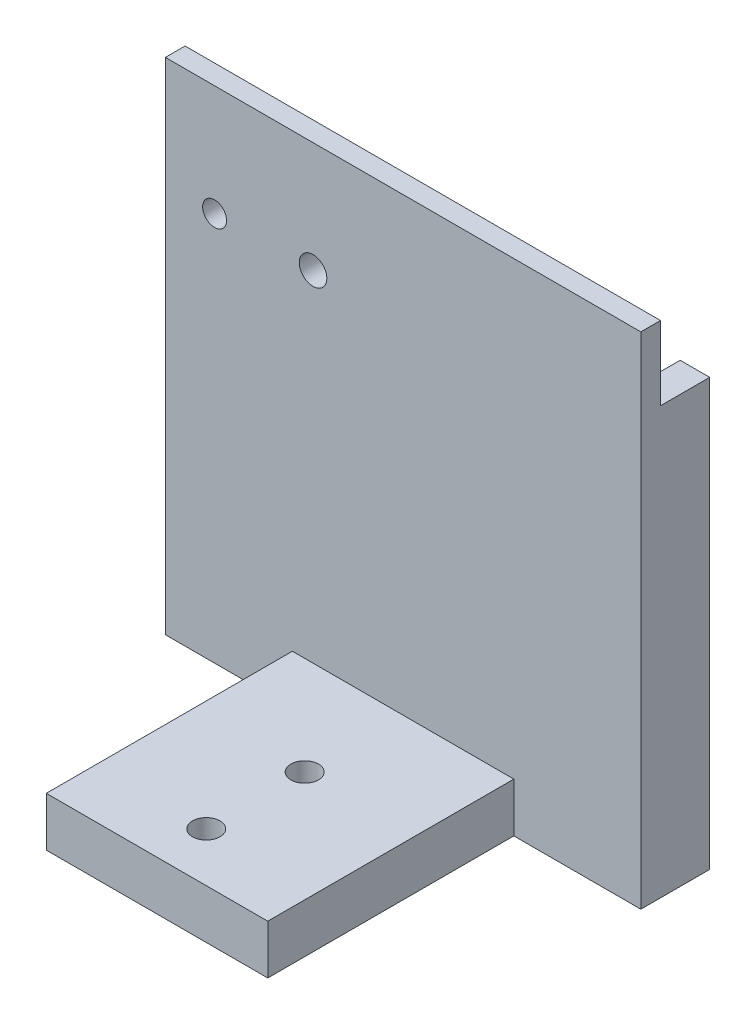
SolidWorks part; units mm, degrees
ref_plane "Front Plane" through (0, 0, 0) normal (0, 0, 1) x (1, 0, 0)
ref_plane "Top Plane" through (0, 0, 0) normal (0, 1, 0) x (1, 0, 0)
ref_plane "Right Plane" through (0, 0, 0) normal (1, 0, 0) x (0, 0, -1)
sketch "Sketch1" plane through (0, 0, 0) normal (0, 0, 1) x (1, 0, 0)
  line L0 (-17.15, 21.15) -> (17.15, 21.15) construction
  line L1 (21.15, -21.15) -> (-21.15, -21.15)
  line L2 (21.15, -21.15) -> (21.15, 21.15)
  line L3 (21.15, 21.15) -> (-21.15, 21.15)
  line L4 (-21.15, -21.15) -> (-21.15, 21.15)
  line L5 (-21.15, -17.15) -> (-21.15, 17.15) construction
  line L6 (21.15, 17.15) -> (21.15, -17.15) construction
  line L7 (17.15, -21.15) -> (-17.15, -21.15) construction
  line L9 (24.15, -22.15) -> (-24.15, -22.15)
  line L10 (24.15, -22.15) -> (24.15, 21.15)
  line L11 (24.15, 21.15) -> (-24.15, 21.15)
  line L12 (-24.15, -22.15) -> (-24.15, 21.15)
  point P16 (-21.15, 0)
  dimension "D1" = 0
  dimension "D2" = 0
  dimension "D3" = 0
  dimension "D4" = 0
  dimension "D5" = 3
  dimension "D6" = 3
  dimension "D7" = 1
  dimension "D8" = 0
extrude "Boss-Extrude1" add sketch "Sketch1" along normal blind 2 contours L4 L1 L2 L3 | L12 L9 L10 L11 L2 L1 L4 region at (21.7987, 0, 0) region at (0, 0, 0)
extrude "Boss-Extrude2" add sketch "Sketch1<3>" against normal blind 5 contours L12 L9 L10 L11 L2 L1 L4 region at (21.7987, 0, 0)
sketch "Sketch1<3>" plane through (0, 0, 0) normal (0, 0, 1) x (1, 0, 0) same geometry as "Sketch1"
sketch "Sketch2" plane through (0, 0, 2) normal (0, 0, 1) x (1, 0, 0)
  line L0 (24.15, -22.15) -> (-24.15, -22.15) construction
  line L1 (11.25, -22.15) -> (-11.25, -22.15)
  line L2 (11.25, -22.15) -> (11.25, -17.15)
  line L3 (11.25, -17.15) -> (-11.25, -17.15)
  line L4 (-11.25, -22.15) -> (-11.25, -17.15)
  line L5 (24.15, -22.15) -> (24.15, 21.15) construction
  dimension "D1" = 22.5
  dimension "D2" = 12.9
  dimension "D3" = 5
extrude "Boss-Extrude3" add sketch "Sketch2" along normal blind 25
sketch "Sketch3" plane through (0, 0, 2) normal (0, 0, 1) x (1, 0, 0)
  line L0 (-110.3641, 28.649) -> (-55.8641, 28.649) construction
  line L1 (-24.15, 6.149) -> (24.15, 6.149)
  line L2 (-24.15, 6.149) -> (-24.15, 28.649)
  line L3 (-24.15, 28.649) -> (24.15, 28.649)
  line L4 (24.15, 6.149) -> (24.15, 28.649)
  line L5 (24.15, -22.15) -> (24.15, 21.15) construction
  line L6 (-24.15, -22.15) -> (-24.15, 21.15) construction
  circle A0 centre (-19.15, 17.399) radius 1.2149
  circle A1 centre (-9.15, 17.399) radius 1.4
  dimension "D5" = 10
  dimension "D6" = 5
  dimension "D7" = 2.8
  dimension "D8" = 11.25
  dimension "D9" = 11.25
  dimension "D1" = 0
  dimension "D2" = 22.5
  dimension "D3" = 0
  dimension "D4" = 0
extrude "Boss-Extrude4" add sketch "Sketch3" against normal blind 2
sketch "Sketch4" plane through (0, -17.15, 0) normal (0, 1, 0) x (1, 0, 0)
  line L0 (11.25, -27) -> (-11.25, -27) construction
  line L1 (-11.25, -27) -> (-11.25, -2) construction
  circle A0 centre (0, -12) radius 1.4
  circle A1 centre (0, -22) radius 1.4
  dimension "D2" = 10
  dimension "D3" = 2.8
  dimension "D4" = 2.8
  dimension "D5" = 11.25
  dimension "D6" = 11.25
  dimension "D1" = 5
extrude "Cut-Extrude1" cut sketch "Sketch4" against normal through all
extrude "Cut-Extrude2" cut sketch "Sketch3<2>" against normal blind 2 contours A1 | A0 region at (-9.15, 17.399, 2)
sketch "Sketch3<2>" plane through (0, 0, 2) normal (0, 0, 1) x (1, 0, 0) same geometry as "Sketch3"
